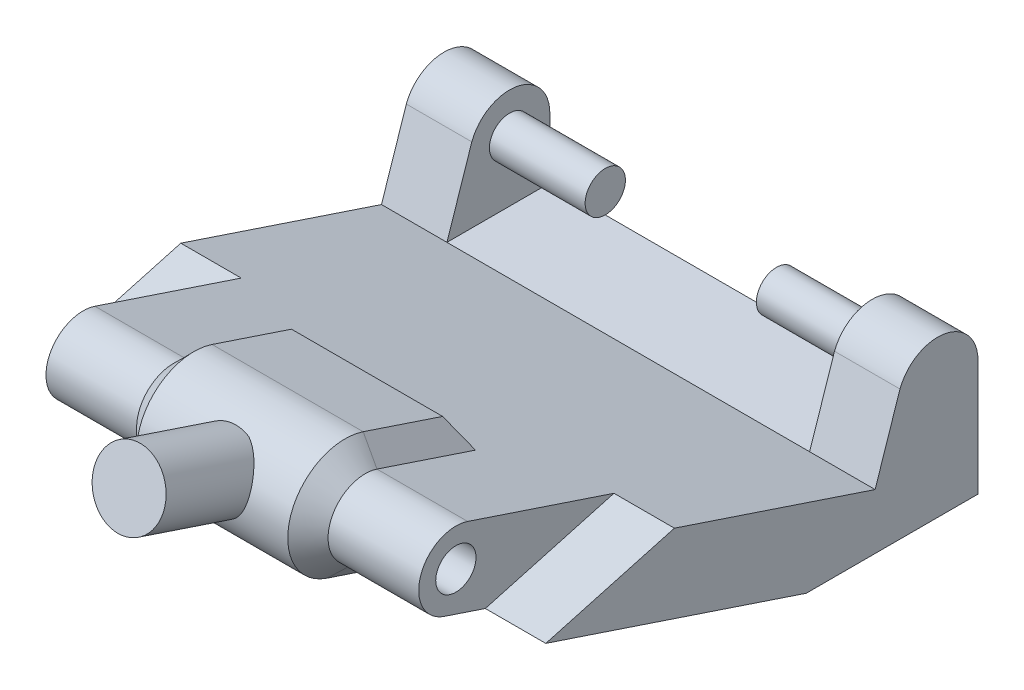
SolidWorks part; units mm, degrees
ref_plane "Front Plane" through (0, 0, 0) normal (0, 0, 1) x (1, 0, 0)
ref_plane "Top Plane" through (0, 0, 0) normal (0, 1, 0) x (1, 0, 0)
ref_plane "Right Plane" through (0, 0, 0) normal (1, 0, 0) x (0, 0, -1)
sketch "Sketch1" plane through (0, 0, 0) normal (0, 0, 1) x (1, 0, 0)
  line L2 (0, -15) -> (24.5, -15)
  line L3 (0, -15) -> (-24.5, -15)
  line L4 (-24.5, -15) -> (-24.5, 24)
  line L5 (-24.5, 24) -> (24.5, 24)
  line L6 (24.5, 24) -> (24.5, -15)
  dimension "D1" = 24.5
  dimension "D2" = 39
  dimension "D3" = 49
extrude "Boss-Extrude1" add sketch "Sketch1" along normal blind 13
chamfer "Chamfer1" distance 13 distance2 39 1 edges at (0, 24, 13)
sketch "Sketch2" plane through (24.5, 0, 0) normal (1, 0, 0) x (0, 0, -1)
  line L1 (0, -15) -> (0, 24) construction
  line L2 (0, 2) -> (-7.3333, 2)
  line L3 (0, 24) -> (-7.3333, 2)
  line L4 (0, 24) -> (-13, -15) construction
  line L5 (0, 2) -> (0, 24)
extrude "Cut-Extrude1" cut sketch "Sketch2" against normal blind 49
sketch "Sketch3" plane through (24.5, 0, 0) normal (1, 0, 0) x (0, 0, -1)
  line L7 (-13, -15) -> (-7.3333, 2)
  line L8 (-13, -15) -> (-12.5467, -15)
  line L10 (-12.5467, -15) -> (-7.7447, -0.5937)
  line L11 (0, -2) -> (0, 2)
  line L12 (0, 2) -> (-7.3333, 2)
  arc A0 (0, -2) -> (-7.7447, -0.5937) centre (-4, -2) ccw
  line M9 (0, -15) -> (0, 2)
  line M10 (0, 2) -> (-7.3333, 2)
  line M11 (-7.3333, 2) -> (-13, -15)
  line M12 (-13, -15) -> (0, -15)
  dimension "D2" = 4
extrude "Cut-Extrude2" cut sketch "Sketch3" against normal blind 49 contours A0 L12 L10 M11 M12 | A0 M9 M10
ref_plane "Plane1" through (18, 0, 0) normal (1, 0, 0) x (0, 0, -1)
sketch "Sketch4" plane through (18, 0, 0) normal (1, 0, 0) x (0, 0, -1)
  line L1 (0, -8) -> (-10.2134, -8)
  line L5 (0, -15) -> (0, -2)
  line L6 (-7.7447, -0.5937) -> (-12.5467, -15)
  line L7 (-12.5467, -15) -> (0, -15)
  line L8 (0, -8) -> (0, -2)
  line L9 (-7.7447, -0.5937) -> (-10.2134, -8)
  arc A1 (0, -2) -> (-7.7447, -0.5937) centre (-4, -2) ccw
  arc A2 (0, -2) -> (-7.7447, -0.5937) centre (-4, -2) ccw
  dimension "D2" = 0
extrude "Cut-Extrude3" cut sketch "Sketch4" against normal blind 36
sketch "Sketch5" plane through (18, 0, 0) normal (-1, 0, 0) x (0, 0, 1)
  circle A0 centre (4, -2) radius 2
  dimension "D1" = 4
extrude "Boss-Extrude2" add sketch "Sketch5" along normal blind 9.5
sketch "Sketch7" plane through (-18, 0, 0) normal (1, 0, 0) x (0, 0, -1)
  circle A0 centre (-4, -2) radius 2
  dimension "D1" = 4
extrude "Boss-Extrude3" add sketch "Sketch7" along normal blind 9.5
sketch "Sketch8" plane through (0, 2.264, 6.7921) normal (0, 0.3162, 0.9487) x (1, 0, 0)
  line L0 (-24.5, -18.1979) -> (-24.5, -3.0123) construction
  line L1 (24.5, -18.1979) -> (-24.5, -18.1979)
  line L2 (24.5, -18.1979) -> (24.5, -10.8192)
  line L3 (24.5, -10.8192) -> (-24.5, -10.8192)
  line L4 (-24.5, -18.1979) -> (-24.5, -10.8192)
extrude "Boss-Extrude4" add sketch "Sketch8" along normal blind 40
sketch "Sketch9" plane through (24.5, 0, 0) normal (1, 0, 0) x (0, 0, -1)
  line L0 (-50.4941, -2.3509) -> (-48.1607, 4.6491) construction
  line L2 (-50.4941, -2.3509) -> (-12.5467, -15) construction
  line L3 (-48.1607, 4.6491) -> (-10.2134, -8) construction
  line L4 (-44.6607, 3.4824) -> (-48.1607, 4.6491)
  line L5 (-48.1607, 4.6491) -> (-50.4941, -2.3509)
  line L6 (-46.9941, -3.5176) -> (-50.4941, -2.3509)
  arc A0 (-44.6607, 3.4824) -> (-46.9941, -3.5176) centre (-45.8274, -0.0176) ccw
  line M6 (-10.2134, -8) -> (-48.1607, 4.6491)
  line M7 (-48.1607, 4.6491) -> (-50.4941, -2.3509)
  line M8 (-50.4941, -2.3509) -> (-12.5467, -15)
  dimension "D1" = 7.3786
  dimension "D2" = 3.6893
  dimension "D3" = 3.6893
extrude "Cut-Extrude4" cut sketch "Sketch9" against normal blind 49 contours A0 L5 M8 | A0 M6 M7
sketch "Sketch10" plane through (24.5, 0, 0) normal (1, 0, 0) x (0, 0, -1)
  line L1 (-46.9941, -3.5176) -> (-12.5467, -15) construction
  line L3 (-44.6607, 3.4824) -> (-10.2134, -8) construction
  line L4 (-42.9046, -4.8807) -> (-30.1358, -1.3592)
  line L10 (-10.2134, -8) -> (-44.6607, 3.4824)
  line L11 (-46.9941, -3.5176) -> (-12.5467, -15)
  line L12 (-12.5467, -15) -> (0, -15)
  line L13 (0, -15) -> (0, -2)
  line L14 (-7.7447, -0.5937) -> (-10.2134, -8)
  line L15 (-30.1358, -1.3592) -> (-44.6607, 3.4824)
  line L16 (-46.9941, -3.5176) -> (-42.9046, -4.8807)
  arc A2 (-44.6607, 3.4824) -> (-46.9941, -3.5176) centre (-45.8274, -0.0176) ccw
  arc A3 (0, -2) -> (-7.7447, -0.5937) centre (-4, -2) ccw
  arc A4 (-44.6607, 3.4824) -> (-46.9941, -3.5176) centre (-45.8274, -0.0176) ccw
  dimension "D1" = 32
  dimension "D2" = 21
  dimension "D3" = 0
extrude "Cut-Extrude5" cut sketch "Sketch10" against normal blind 6
sketch "Sketch11" plane through (-24.5, 0, 0) normal (-1, 0, 0) x (0, 0, 1)
  line L1 (46.9941, -3.5176) -> (12.5467, -15) construction
  line L3 (44.6607, 3.4824) -> (10.2134, -8) construction
  line L4 (30.1358, -1.3592) -> (42.9046, -4.8807)
  line L10 (44.6607, 3.4824) -> (10.2134, -8)
  line L11 (10.2134, -8) -> (7.7447, -0.5937)
  line L12 (0, -2) -> (0, -15)
  line L13 (0, -15) -> (12.5467, -15)
  line L14 (12.5467, -15) -> (46.9941, -3.5176)
  line L15 (44.6607, 3.4824) -> (30.1358, -1.3592)
  line L19 (42.9046, -4.8807) -> (46.9941, -3.5176)
  arc A2 (46.9941, -3.5176) -> (44.6607, 3.4824) centre (45.8274, -0.0176) ccw
  arc A3 (7.7447, -0.5937) -> (0, -2) centre (4, -2) ccw
  arc A4 (46.9941, -3.5176) -> (44.6607, 3.4824) centre (45.8274, -0.0176) ccw
  dimension "D1" = 32
  dimension "D2" = 21
  dimension "D3" = 0
extrude "Cut-Extrude6" cut sketch "Sketch11" against normal blind 6
sketch "Sketch12" plane through (-18.5, 0, 0) normal (-1, 0, 0) x (0, 0, 1)
  circle A0 centre (45.8274, -0.0176) radius 2
  dimension "D1" = 4
extrude "Cut-Extrude7" cut sketch "Sketch12" against normal blind 37
ref_plane "Plane2" through (7.5, 0, 0) normal (1, 0, 0) x (0, 0, -1)
sketch "Sketch13" plane through (7.5, 0, 0) normal (1, 0, 0) x (0, 0, -1)
  line L0 (-36.1441, 2.7517) -> (-44.0283, 5.3798)
  line L1 (-47.6265, -5.4149) -> (-43.5371, -6.7781)
  line L2 (-43.5371, -6.7781) -> (-39.7423, -8.043)
  line L3 (-46.9941, -3.5176) -> (-42.9046, -4.8807)
  line L4 (-42.9046, -4.8807) -> (-30.1358, -1.3592)
  line L5 (-30.1358, -1.3592) -> (-44.6607, 3.4824)
  line L6 (-10.2134, -8) -> (-30.1358, -1.3592)
  line L7 (-30.1358, -1.3592) -> (-42.9046, -4.8807)
  line L8 (-42.9046, -4.8807) -> (-12.5467, -15)
  line L9 (-12.5467, -15) -> (0, -15)
  line L10 (0, -15) -> (0, -2)
  line L11 (-7.7447, -0.5937) -> (-10.2134, -8)
  line L12 (-39.1099, -6.1456) -> (-39.7423, -8.043)
  line L14 (-42.9046, -4.8807) -> (-39.1099, -6.1456)
  line L18 (-46.9941, -3.5176) -> (-42.9046, -4.8807)
  line L20 (-36.7765, 0.8544) -> (-44.6607, 3.4824)
  line L26 (-36.1441, 2.7517) -> (-36.7765, 0.8544)
  line L27 (-43.5371, -6.7781) -> (-12.8713, -17) construction
  line L28 (-42.9046, -4.8807) -> (-12.5467, -15) construction
  line L29 (-10.2134, -8) -> (-30.1358, -1.3592) construction
  line L30 (-11.4783, -5.4702) -> (-29.5033, 0.5381) construction
  line L31 (0, -15) -> (0, -2) construction
  line L32 (-9.6314, 0.0707) -> (-11.4783, -5.4702) construction
  line L33 (2, -17) -> (2, -2) construction
  line L34 (-7.7447, -0.5937) -> (-10.2134, -8) construction
  line L35 (-12.5467, -15) -> (0, -15) construction
  line L36 (-12.8713, -17) -> (2, -17) construction
  line L37 (-30.1358, -1.3592) -> (-44.6607, 3.4824) construction
  line L38 (-29.5033, 0.5381) -> (-44.0283, 5.3798) construction
  arc A0 (-44.0283, 5.3798) -> (-47.6265, -5.4149) centre (-45.8274, -0.0176) ccw
  arc A1 (0, -2) -> (-7.7447, -0.5937) centre (-4, -2) ccw
  arc A3 (-44.6607, 3.4824) -> (-46.9941, -3.5176) centre (-45.8274, -0.0176) ccw
  arc A4 (-44.6607, 3.4824) -> (-46.9941, -3.5176) centre (-45.8274, -0.0176) ccw
  arc A6 (2, -2) -> (-9.6314, 0.0707) centre (-4, -2) ccw construction
  arc A7 (0, -2) -> (-7.7447, -0.5937) centre (-4, -2) ccw construction
  dimension "D4" = 8.3107
  dimension "D1" = 0
  dimension "D2" = 0
  dimension "D3" = 2
extrude "Boss-Extrude5" add sketch "Sketch13" against normal blind 15
chamfer "Chamfer2" distance 2 distance2 2 8 edges at (0, 0.8544, 36.7765) (-7.5, 2.1684, 40.7186) (7.5, 2.1684, 40.7186) (-7.5, 1.1491, 49.3274) (7.5, 1.1491, 49.3274) (-7.5, -4.8316, 43.052) (0, -6.1456, 39.1099) (7.5, -4.8316, 43.052)
ref_plane "Plane3" through (-7.5, 1.7816, 51.2248) normal (0, 0.3162, 0.9487) x (1, 0, 0)
sketch "Sketch14" plane through (-7.5, 1.7816, 51.2248) normal (0, 0.3162, 0.9487) x (1, 0, 0)
  line L0 (0, 5.6893) -> (0, -5.6893) construction
  circle A0 centre (7.5, 0) radius 3.5
  point P6 (0, 0)
  dimension "D2" = 7
  dimension "D3" = 7.5
  dimension "D1" = 5.6893
extrude "Boss-Extrude6" add sketch "Sketch14" along normal blind 10 from offset 1
sketch "Sketch16" plane through (24.5, 0, 0) normal (1, 0, 0) x (0, 0, -1)
  line L0 (-42.9046, -4.8807) -> (-12.5467, -15) construction
  line L1 (0, -15) -> (-17.0467, -15)
  line L2 (0, -15) -> (0, -13.5)
  line L3 (0, -13.5) -> (-17.0467, -13.5)
  line L4 (-17.0467, -15) -> (-17.0467, -13.5)
  dimension "D1" = 1.5
extrude "Cut-Extrude8" cut sketch "Sketch16" against normal blind 49
